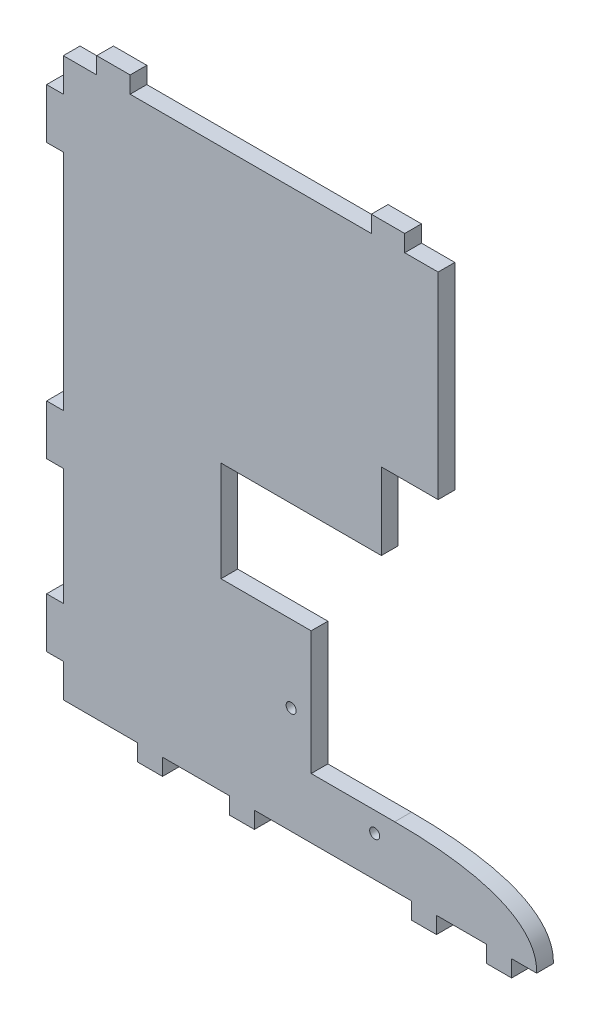
SolidWorks part; units mm, degrees
ref_plane "Plan de face" through (0, 0, 0) normal (0, 0, 1) x (1, 0, 0)
ref_plane "Plan de dessus" through (0, 0, 0) normal (0, 1, 0) x (1, 0, 0)
ref_plane "Plan de droite" through (0, 0, 0) normal (1, 0, 0) x (0, 0, -1)
sketch "Esquisse1" plane through (0, 0, 0) normal (0, 0, 1) x (1, 0, 0)
  line L1 (0, 0) -> (37, 0)
  line L2 (0, 0) -> (0, 55)
  line L3 (0, 55) -> (12, 55)
  line L4 (37, 0) -> (37, 18)
  line L6 (12, 55) -> (12, 18)
  line L7 (12, 18) -> (37, 18)
  circle A0 centre (6, 32) radius 1.5
  circle A1 centre (31, 12) radius 1.5
  dimension "D3" = 20
  dimension "D4" = 3
  dimension "D1" = 6
  dimension "D2" = 55
  dimension "D5" = 12
  dimension "D7" = 25
  dimension "D8" = 6
  dimension "D9" = 6
extrude "Boss.-Extru.1" add sketch "Esquisse1" along normal blind 5
sketch "Esquisse2" plane through (0, 0, 5) normal (0, 0, 1) x (1, 0, 0)
  line L0 (37, 18) -> (12, 18) construction
  line L1 (37, 0) -> (42, 0)
  line L2 (37, 0) -> (37, 18)
  line L3 (49.5, 0) -> (64.5, 0)
  line L4 (12, 55) -> (0, 55) construction
  line L5 (72, 0) -> (72, -5)
  line L6 (72, -5) -> (64.5, -5)
  line L7 (64.5, 0) -> (64.5, -5)
  line L8 (72, 0) -> (79.5, 0)
  line L9 (49.5, 0) -> (49.5, -5)
  line L10 (49.5, -5) -> (42, -5)
  line L11 (42, 0) -> (42, -5)
  line L12 (0, 0) -> (-5, 0)
  line L13 (0, 0) -> (0, 55)
  line L14 (0, 55) -> (-15, 55)
  line L15 (40, 167) -> (50, 167)
  line L16 (-12.5, 0) -> (-32.5, 0)
  line L17 (-40, 0) -> (-40, -5)
  line L18 (-15, 55) -> (-15, 85)
  line L19 (-40, -5) -> (-32.5, -5)
  line L20 (-62.19, 0) -> (-62.19, 10)
  line L21 (-62.19, 167) -> (-52.19, 167)
  line L22 (-32.5, 0) -> (-32.5, -5)
  line L23 (33, 85) -> (-15, 85)
  line L24 (50, 167) -> (50, 108)
  line L25 (-12.5, 0) -> (-12.5, -5)
  line L26 (-12.5, -5) -> (-5, -5)
  line L27 (-5, 0) -> (-5, -5)
  line L28 (-40, 0) -> (-62.19, 0)
  line L29 (-52.19, 167) -> (-52.19, 172)
  line L30 (-52.19, 172) -> (-42.19, 172)
  line L31 (-42.19, 167) -> (-42.19, 172)
  line L32 (-42.19, 167) -> (30, 167)
  line L33 (40, 167) -> (40, 172)
  line L34 (40, 172) -> (30, 172)
  line L35 (30, 167) -> (30, 172)
  line L36 (-62.19, 157) -> (-62.19, 167)
  line L37 (-62.19, 10) -> (-67.19, 10)
  line L38 (33, 85) -> (33, 108)
  line L39 (33, 108) -> (50, 108)
  line L41 (-62.19, 25) -> (-67.19, 25)
  line L42 (-67.19, 10) -> (-67.19, 25)
  line L43 (-62.19, 60) -> (-67.19, 60)
  line L44 (-62.19, 25) -> (-62.19, 60)
  line L45 (-62.19, 75) -> (-67.19, 75)
  line L46 (-67.19, 60) -> (-67.19, 75)
  line L47 (-62.19, 157) -> (-67.19, 157)
  line L48 (-62.19, 75) -> (-62.19, 142)
  line L49 (-62.19, 142) -> (-67.19, 142)
  line L50 (-67.19, 157) -> (-67.19, 142)
  spline S0 degree 3 poles (37, 18) (79.2395, 18) (79.5, 3.8743) (79.5, 0) knots 0 0 0 0 1 1 1 1
  dimension "D1" = 42.5
  dimension "D2" = 7.5
  dimension "D3" = 5
  dimension "D4" = 5
  dimension "D5" = 15
  dimension "D6" = 15
  dimension "D7" = 30
  dimension "D8" = 167
  dimension "D9" = 23
  dimension "D10" = 5
  dimension "D11" = 20
  dimension "D12" = 62.19
  dimension "D13" = 50
  dimension "D14" = 5
  dimension "D15" = 10
  dimension "D16" = 10
  dimension "D17" = 10
  dimension "D18" = 17
  dimension "D19" = 10
  dimension "D20" = 10
  dimension "D21" = 35
  dimension "D22" = 15
  dimension "D23" = 5
extrude "Boss.-Extru.2" add sketch "Esquisse2" against normal blind 5
